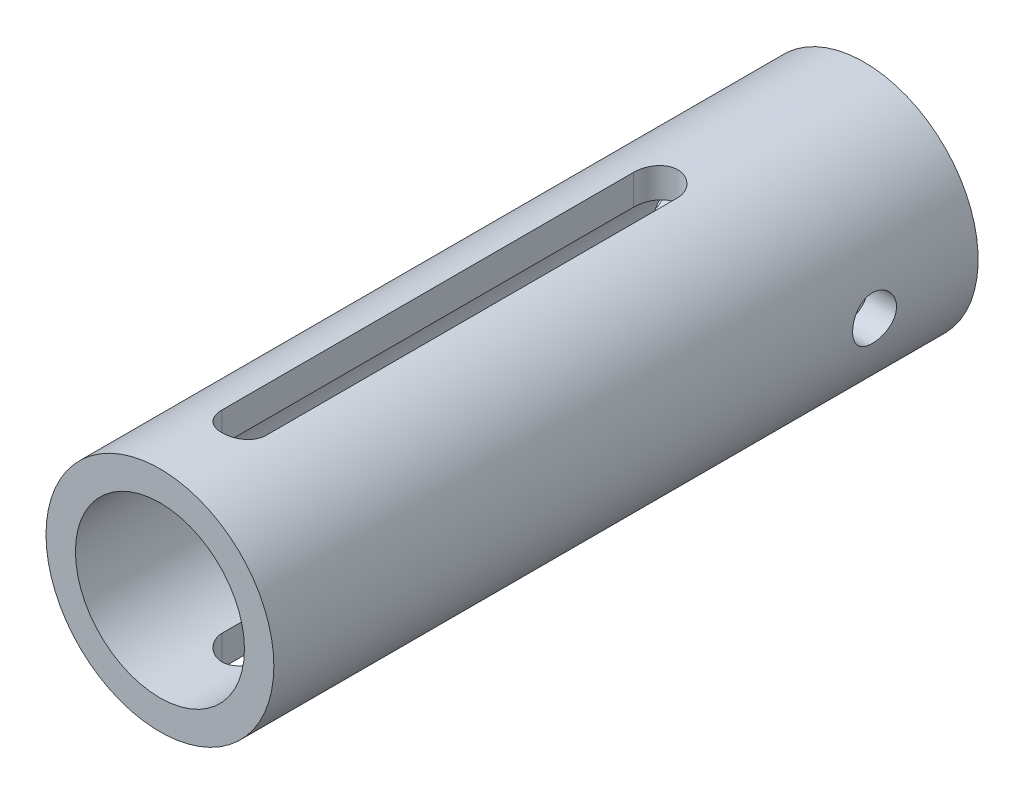
SolidWorks part; units mm, degrees
ref_plane "Front" through (0, 0, 0) normal (0, 0, 1) x (1, 0, 0)
ref_plane "Top" through (0, 0, 0) normal (0, 1, 0) x (1, 0, 0)
ref_plane "Right" through (0, 0, 0) normal (1, 0, 0) x (0, 0, -1)
sketch "Sketch1" plane through (0, 0, 0) normal (0, 0, 1) x (1, 0, 0)
  circle A0 centre (0, 0) radius 17.4625
  circle A1 centre (0, 0) radius 12.954
  dimension "D1" = 34.925
  dimension "D2" = 25.908
extrude "Boss-Extrude1" add sketch "Sketch1" along normal blind 101.6
hole_wizard "1/4 Clearance Slot1" positions "Sketch3" profile "Sketch2" size "1/4" standard "ANSI Inch" slot yes end condition through all
sketch "Sketch3" plane through (0, 0, 0) normal (0, 1, 0) x (1, 0, 0)
  line L0 (0, -92.075) -> (0, -22.225) construction
  line L1 (-17.4625, -101.6) -> (17.4625, -101.6) construction
  point P0 (0, -57.15)
  dimension "D1" = 9.525
sketch "Sketch2" plane through (0, 0, 57.15) normal (1, 0, 0) x (0, 0, -1)
  line L0 (0, 0) -> (0, 17.4625)
  line L1 (0, 17.4625) -> (3.3782, 17.4625)
  line L2 (3.3782, 17.4625) -> (3.3782, 0)
  line L5 (3.3782, 0) -> (0, 0)
  line L11 (0, -6.35) -> (0, 107.95) construction
  dimension "Thru Hole Dia." = 6.7564
  dimension "Thru Hole Depth" = 17.4625
sketch "Sketch4" plane through (0, 0, 0) normal (0, 1, 0) x (1, 0, 0)
  line L0 (-3.3782, -88.6968) -> (-3.3782, -25.6032) construction
  line L1 (3.3782, -88.6968) -> (3.3782, -25.6032) construction
  line L2 (-3.3782, -88.6968) -> (-3.3782, -25.6032)
  line L3 (3.3782, -88.6968) -> (3.3782, -25.6032)
  arc A0 (3.3782, -25.6032) -> (-3.3782, -25.6032) centre (0, -25.6032) ccw construction
  arc A1 (-3.3782, -88.6968) -> (3.3782, -88.6968) centre (0, -88.6968) ccw construction
  arc A2 (3.3782, -25.6032) -> (-3.3782, -25.6032) centre (0, -25.6032) ccw
  arc A3 (-3.3782, -88.6968) -> (3.3782, -88.6968) centre (0, -88.6968) ccw
extrude "Cut-Extrude1" cut sketch "Sketch4" against normal up to next
sketch "Sketch7" plane through (0, 0, 0) normal (0, 0, -1) x (-1, 0, 0)
  circle A0 centre (0, 0) radius 15.875
extrude "Boss-Extrude2" [suppressed] add sketch "Sketch7" against normal blind 15.875
sketch "Sketch6" plane through (0, 0, 0) normal (1, 0, 0) x (0, 0, -1)
  circle A0 centre (-9.525, 0) radius 3.3655
extrude "Cut-Extrude3" cut sketch "Sketch6" against normal through all and the other way through all
sketch "Sketch8" plane through (0, 0, 0) normal (0, 0, -1) x (-1, 0, 0)
  circle A0 centre (0, 0) radius 17.4625
  dimension "D1" = 34.925
extrude "Boss-Extrude3" add sketch "Sketch8" along normal blind 6.35
